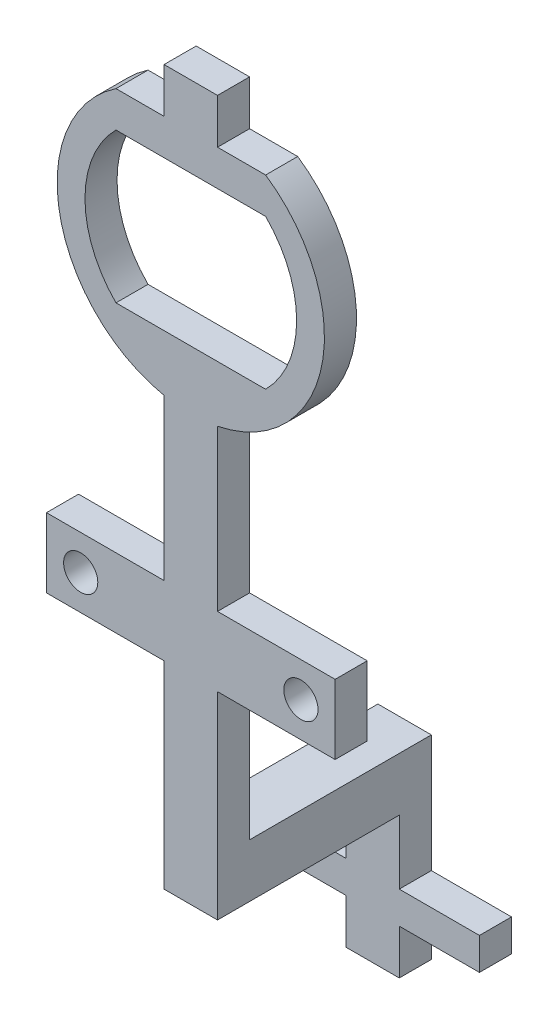
SolidWorks part; units mm, degrees
ref_plane "Front Plane" through (0, 0, 0) normal (0, 0, 1) x (1, 0, 0)
ref_plane "Top Plane" through (0, 0, 0) normal (0, 1, 0) x (1, 0, 0)
ref_plane "Right Plane" through (0, 0, 0) normal (1, 0, 0) x (0, 0, -1)
sketch "Sketch1" plane through (0, 0, 0) normal (0, 0, 1) x (1, 0, 0)
  line L0 (-7, 7.0007) -> (7, 7.0007)
  line L5 (-18.4746, 0) -> (14.4817, 0) construction
  line L6 (-7, -7.0007) -> (7, -7.0007)
  line L7 (-7, 10.3562) -> (7, 10.3562)
  line L8 (0, 0) -> (0, 29.3453) construction
  line L11 (-2.5, -7.0007) -> (2.3856, -7.0007)
  line L13 (2.5, -52.2474) -> (2.5, -12.2474)
  line L18 (-2.5, -52.2474) -> (-2.5, -12.2474)
  line L21 (2.5, -52.2474) -> (-2.5, -52.2474)
  arc A0 (-7, 7.0007) -> (-7, -7.0007) centre (0, 0) ccw
  arc A1 (7, -7.0007) -> (7, 7.0007) centre (0, 0) ccw
  arc A2 (-7, 10.3562) -> (-2.5, -12.2474) centre (0, 0) ccw
  arc A3 (2.5, -12.2474) -> (7, 10.3562) centre (0, 0) ccw
  dimension "D1" = 19.8
  dimension "D3" = 25
  dimension "D4" = 40
  dimension "D2" = 14
  dimension "D5" = 5
  dimension "D6" = 5.2467
  dimension "D7" = 4.5
extrude "Boss-Extrude1" add sketch "Sketch1" along normal blind 3 contours A3 L7 A2 A1 L6 A0 L0 region at (0, -15.9639, 0)
sketch "Sketch3" plane through (0, 0, 0) normal (0, 0, 1) x (1, 0, 0)
  line L0 (0, -46.1586) -> (0, 0.6217) construction
  line L1 (13.5, -27.2474) -> (-13.5, -27.2474)
  line L2 (13.5, -27.2474) -> (13.5, -33.7474)
  line L3 (13.5, -33.7474) -> (-13.5, -33.7474)
  line L4 (-13.5, -27.2474) -> (-13.5, -33.7474)
  line L5 (13.5, -27.2474) -> (-13.5, -33.7474) construction
  line L6 (13.5, -33.7474) -> (-13.5, -27.2474) construction
  line L8 (2.5, -52.2474) -> (-2.5, -52.2474) construction
  circle A0 centre (-10.3, -30.4974) radius 1.6
  circle A1 centre (10.3, -30.4974) radius 1.6
  point P0 (0, -30.4974)
  dimension "D4" = 3.2
  dimension "D5" = 3.2
  dimension "D6" = 3.25
  dimension "D1" = 27
  dimension "D2" = 6.5
  dimension "D3" = 18.5
sketch "Sketch4" plane through (0, 10.3562, 0) normal (0, 1, 0) x (1, 0, 0)
  line L0 (-7, 0) -> (7, 0) construction
  line L1 (2.5, -3) -> (-2.5, -3)
  line L2 (2.5, -3) -> (2.5, 0)
  line L3 (2.5, 0) -> (-2.5, 0)
  line L4 (-2.5, -3) -> (-2.5, 0)
  line L5 (2.5, -3) -> (-2.5, 0) construction
  line L6 (2.5, 0) -> (-2.5, -3) construction
  line L7 (-7, -3) -> (7, -3) construction
  line L8 (-7, -3) -> (-7, 0) construction
  point P0 (0, -1.5)
  point P14 (0, 0)
  dimension "D1" = 5
  dimension "D2" = 4.5
extrude "Boss-Extrude4" add sketch "Sketch3" along normal blind 3
extrude "Boss-Extrude3" add sketch "Sketch4" along normal blind 4.2
sketch "Sketch6" plane through (0, 0, 0) normal (0, 0, -1) x (-1, 0, 0)
  line L0 (2.5, -52.2474) -> (2.5, -33.7474) construction
  line L1 (-2.5, -52.2474) -> (2.5, -52.2474)
  line L2 (-2.5, -52.2474) -> (-2.5, -47.2474)
  line L3 (-2.5, -47.2474) -> (2.5, -47.2474)
  line L4 (2.5, -52.2474) -> (2.5, -47.2474)
  dimension "D1" = 5
extrude "Boss-Extrude5" add sketch "Sketch6" along normal blind 17
sketch "Sketch9" plane through (0, 0, -17) normal (0, 0, -1) x (-1, 0, 0)
  line L0 (2.5, -61.2438) -> (2.5, -65.4438)
  line L1 (-2.5, -52.2474) -> (2.5, -52.2474)
  line L2 (-2.5, -52.2474) -> (-2.5, -58.2438)
  line L3 (-2.5, -65.4438) -> (2.5, -65.4438)
  line L4 (2.5, -52.2474) -> (2.5, -58.2438)
  line L5 (10, -58.2438) -> (2.5, -58.2438)
  line L6 (10, -58.2438) -> (10, -61.2438)
  line L7 (10, -61.2438) -> (2.5, -61.2438)
  line L8 (-10, -58.2438) -> (-10, -61.2438)
  line L9 (-2.5, -61.2438) -> (-2.5, -65.4438)
  line L10 (-2.5, -58.2438) -> (-10, -58.2438)
  line L11 (-2.5, -61.2438) -> (-10, -61.2438)
  line L12 (-2.5, 14.5562) -> (2.5, 14.5562) construction
  dimension "D1" = 80
  dimension "D2" = 4.2
  dimension "D3" = 20
  dimension "D4" = 5
  dimension "D5" = 3
extrude "Boss-Extrude6" add sketch "Sketch9" against normal blind 3
